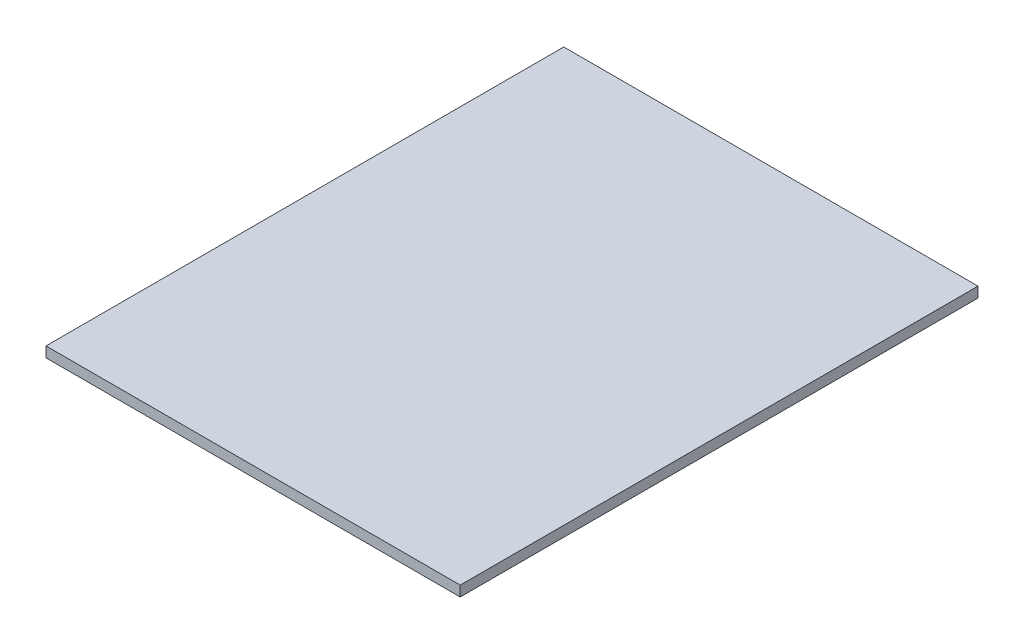
SolidWorks part; units mm, degrees
material "Corrugated Paper"
ref_plane "Front Plane" through (0, 0, 0) normal (0, 0, 1) x (1, 0, 0)
ref_plane "Top Plane" through (0, 0, 0) normal (0, 1, 0) x (1, 0, 0)
ref_plane "Right Plane" through (0, 0, 0) normal (1, 0, 0) x (0, 0, -1)
sketch "Sketch1" plane through (0, 0, 0) normal (0, 1, 0) x (1, 0, 0)
  line L1 (0, 0) -> (200, 0)
  line L2 (0, 0) -> (0, 250)
  line L3 (0, 250) -> (200, 250)
  line L4 (200, 0) -> (200, 250)
  dimension "D1" = 250
  dimension "D2" = 200
extrude "Boss-Extrude1" add sketch "Sketch1" along normal blind 5
